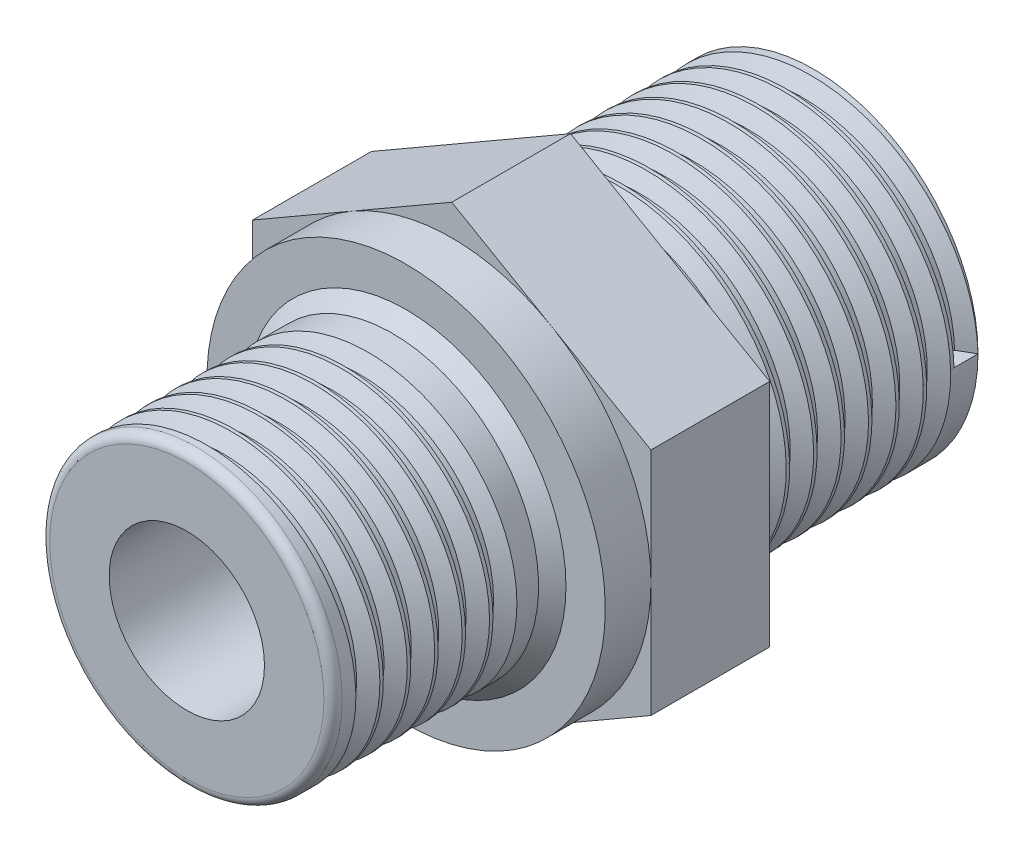
SolidWorks part; units mm, degrees
material "AISI 304"
ref_plane "Ön Düzlem" through (0, 0, 0) normal (0, 0, 1) x (1, 0, 0)
ref_plane "Üst Düzlem" through (0, 0, 0) normal (0, 1, 0) x (1, 0, 0)
ref_plane "Sağ Düzlem" through (0, 0, 0) normal (1, 0, 0) x (0, 0, -1)
sketch "Çizim13" plane through (0, 0, 0) normal (0, 0, 1) x (1, 0, 0)
  line L1 (0, -12.5862) -> (10.9, -6.2931)
  line L2 (10.9, -6.2931) -> (10.9, 6.2931)
  line L3 (10.9, 6.2931) -> (0, 12.5862)
  line L4 (0, 12.5862) -> (-10.9, 6.2931)
  line L5 (-10.9, 6.2931) -> (-10.9, -6.2931)
  line L6 (-10.9, -6.2931) -> (0, -12.5862)
  circle A0 centre (0, 0) radius 10.9 construction
  dimension "D1" = 21.8
extrude "Yükseklik-Ekstrüzyon4" add sketch "Çizim13" along normal blind 6.5
sketch "Çizim14" plane through (0, 0, 6.5) normal (0, 0, 1) x (1, 0, 0)
  circle A0 centre (0, 0) radius 10.9
  dimension "D1" = 21.8
extrude "Yükseklik-Ekstrüzyon5" add sketch "Çizim14" along normal blind 2.5
sketch "Çizim15" plane through (0, 0, 0) normal (0, 0, -1) x (-1, 0, 0)
  circle A0 centre (0, 0) radius 9
extrude "Yükseklik-Ekstrüzyon6" add sketch "Çizim15" along normal blind 13.3
sketch "Çizim16" plane through (0, 0, 9) normal (0, 0, 1) x (1, 0, 0)
  circle A0 centre (0, 0) radius 8.75
  dimension "D1" = 17.5
extrude "Yükseklik-Ekstrüzyon7" add sketch "Çizim16" along normal blind 2
sketch "Çizim17" plane through (0, 0, 11) normal (0, 0, 1) x (1, 0, 0)
  circle A0 centre (0, 0) radius 8
extrude "Yükseklik-Ekstrüzyon8" add sketch "Çizim17" along normal blind 10
chamfer "Pah1" distance 2 angle 45 1 edges at (8.75, 0, 11)
sketch "Çizim18" plane through (0, 0, 21) normal (0, 0, 1) x (1, 0, 0)
  circle A0 centre (0, 0) radius 4.25
extrude "Kes-Ekstrüzyon3" cut sketch "Çizim18" against normal blind 100
fillet "Radyus1" radius 0.5 1 edges at (8, 0, 21)
sketch "Çizim19" plane through (0, 0, -13.3) normal (0, 0, -1) x (-1, 0, 0)
  circle A0 centre (0, 0) radius 6.15
extrude "Kes-Ekstrüzyon5" cut sketch "Çizim19" against normal blind 3.5 contours A0
chamfer "Pah2" distance 3.5 angle 45 1 edges at (-6.15, 0, -9.8)
thread "Diş4" pitch 1.5 method cut profile "Diş Profili4" start angle 0, offset 0, length 11, pitch 1.5, diameter 18
ref_plane "Düzlem4" through (9, 0, -13.3) normal (0, -1, 0) x (1, 0, 0)
sketch "Diş Profili4" plane through (9, 0, -13.3) normal (0, -1, 0) x (1, 0, 0)
  line L0 (0, 0) -> (0, 1.5) construction
  line L11 (0, 0) -> (0, 1.3125)
  line L12 (0, 1.3125) -> (-0.8119, 0.8437)
  line L13 (-0.8119, 0.8437) -> (-0.8119, 0.4687)
  line L15 (-0.8119, 0.4687) -> (0, 0)
  line L17 (-0.8119, 0.6562) -> (0, 0.6562) construction
  point P2 (0, 0)
  dimension "Pitch" = 1.5
  dimension "Profile_Angle" = 60
  dimension "Profile_Land" = 0.375
  dimension "Profile_Height" = 0.8119
thread "Diş5" pitch 1.5 method cut profile "Diş Profili5" start angle 0, offset 0, length 8.5, pitch 1.5, diameter 16
ref_plane "Düzlem5" through (-8, 0, 20.5) normal (0, -1, 0) x (-1, 0, 0)
sketch "Diş Profili5" plane through (-8, 0, 20.5) normal (0, -1, 0) x (-1, 0, 0)
  line L0 (0, 0) -> (0, 1.5) construction
  line L11 (0, 0) -> (0, 1.3125)
  line L12 (0, 1.3125) -> (-0.8119, 0.8437)
  line L13 (-0.8119, 0.8437) -> (-0.8119, 0.4687)
  line L15 (-0.8119, 0.4687) -> (0, 0)
  line L17 (-0.8119, 0.6562) -> (0, 0.6562) construction
  point P2 (0, 0)
  dimension "Pitch" = 1.5
  dimension "Profile_Angle" = 60
  dimension "Profile_Land" = 0.375
  dimension "Profile_Height" = 0.8119
